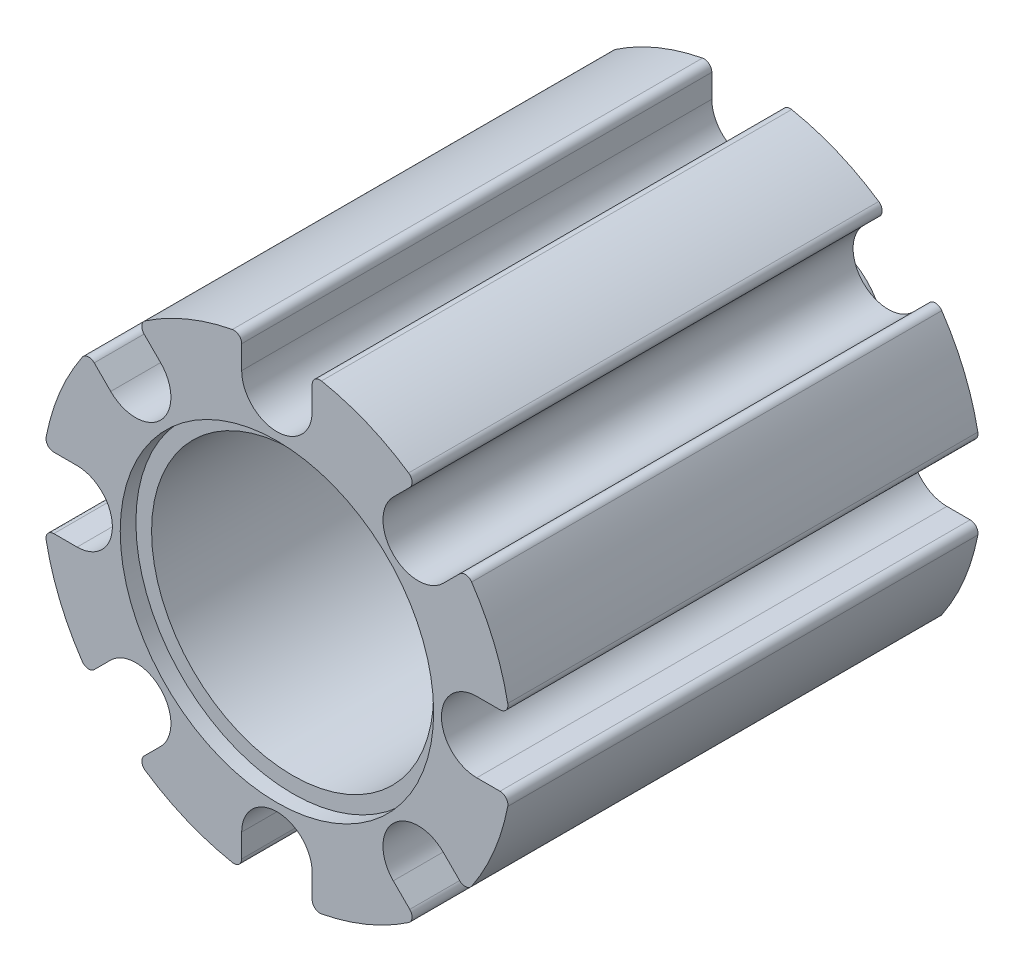
SolidWorks part; units mm, degrees
ref_plane "前视基准面" through (0, 0, 0) normal (0, 0, 1) x (1, 0, 0)
ref_plane "上视基准面" through (0, 0, 0) normal (0, 1, 0) x (1, 0, 0)
ref_plane "右视基准面" through (0, 0, 0) normal (1, 0, 0) x (0, 0, -1)
sketch "草图1" plane through (0, 0, 0) normal (0, 0, 1) x (1, 0, 0)
  line L0 (-22.9562, 0) -> (18.7081, 0) construction
  line L1 (-12.75, 2.25) -> (-14.8303, 2.25)
  line L2 (-12.75, -2.25) -> (-14.8303, -2.25)
  arc A0 (-14.8303, -2.25) -> (-14.8303, 2.25) centre (0, 0) ccw
  arc A1 (-12.75, -2.25) -> (-12.75, 2.25) centre (-12.75, 0) ccw
  circle A9 centre (0, 0) radius 2.5
  point P47 (0, 0)
  dimension "D1" = 4.5
  dimension "D2" = 30
  dimension "D4" = 5
extrude "凸台-拉伸1" add sketch "草图1" along normal blind 30
fillet "圆角1" radius 0.5 2 edges at (-14.8303, -2.25, 15) (-14.8303, 2.25, 15)
sketch "草图3" plane through (0, 0, 30) normal (0, 0, 1) x (1, 0, 0)
  circle A0 centre (0, 0) radius 10
  dimension "D1" = 20
extrude "切除-拉伸1" cut sketch "草图3" against normal blind 1
sketch "草图4" plane through (0, 0, 29) normal (0, 0, 1) x (1, 0, 0)
  circle A0 centre (0, 0) radius 9
  dimension "D1" = 18
extrude "切除-拉伸2" cut sketch "草图4" against normal blind 20
sketch "草图5" plane through (0, 0, 0) normal (0, 0, -1) x (-1, 0, 0)
  circle A0 centre (0, 0) radius 9
  dimension "D1" = 18
extrude "切除-拉伸3" [suppressed] cut sketch "草图5" against normal blind 0.5
sketch "草图2" [suppressed] plane through (0, 0, 0.5) normal (0, 0, -1) x (-1, 0, 0)
  circle A0 centre (0, 0) radius 3.5
  circle A1 centre (0, 0) radius 2.5 construction
  circle A2 centre (0, 0) radius 2.5
  dimension "D1" = 7
extrude "凸台-拉伸2" [suppressed] add sketch "草图2" along normal blind 1
chamfer "倒角1" distance 0.5 angle 45 1 edges at (2.5, 0, 9)
pattern_circular "阵列(圆周)3" count 8 over 360 about axis through (0, 0, 30) along (0, 0, -1) of face at (-13.4934, 2.25, 15) of face at (-11.625, 0, 15) of face at (-13.4934, -2.25, 15) of face at (-14.5524, 2.4896, 15) of face at (-14.5524, -2.4896, 15)
sketch "草图9" plane through (0, 0, 0) normal (0, 0, -1) x (-1, 0, 0)
  circle A0 centre (0, 0) radius 2.5 construction
  circle A1 centre (0, 0) radius 2.5
  circle A2 centre (0, 0) radius 6
  dimension "D1" = 12
extrude "凸台-拉伸3" add sketch "草图9" along normal blind 1.5 separate body
sketch "草图10" plane through (0, 0, -1.5) normal (0, 0, -1) x (-1, 0, 0)
  circle A0 centre (0, 0) radius 2.5 construction
  circle A1 centre (0, 0) radius 2.5
  circle A2 centre (0, 0) radius 3.75
  dimension "D1" = 7.5
extrude "凸台-拉伸4" add sketch "草图10" along normal blind 3.5
